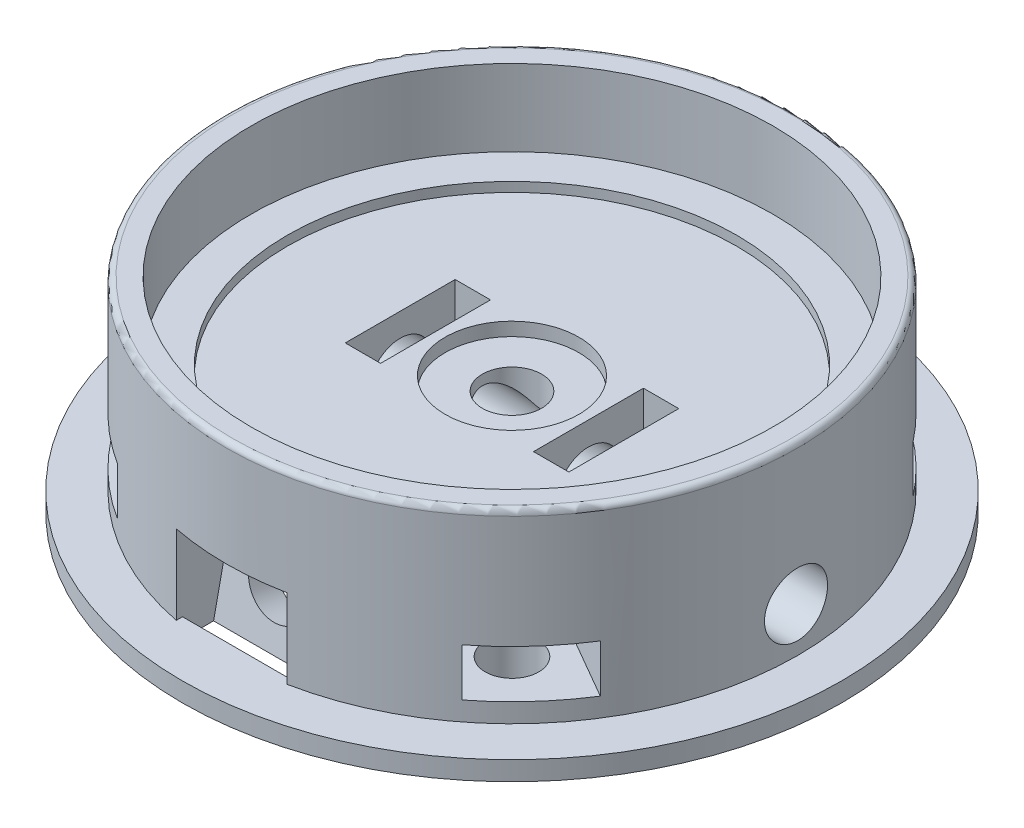
SolidWorks part; units mm, degrees
ref_plane "Front Plane" through (0, 0, 0) normal (0, 0, 1) x (1, 0, 0)
ref_plane "Top Plane" through (0, 0, 0) normal (0, 1, 0) x (1, 0, 0)
ref_plane "Right Plane" through (0, 0, 0) normal (1, 0, 0) x (0, 0, -1)
sketch "Sketch1" plane through (0, 0, 0) normal (0, 1, 0) x (1, 0, 0)
  circle A0 centre (0, 0) radius 14.95
  dimension "D1" = 29.9
extrude "Boss-Extrude1" add sketch "Sketch1" along normal blind 5.7
sketch "Sketch2" plane through (0, 5.7, 0) normal (0, 1, 0) x (1, 0, 0)
  circle A0 centre (0, 0) radius 11.75
  dimension "D1" = 23.5
extrude "Cut-Extrude1" cut sketch "Sketch2" against normal blind 0.5
sketch "Sketch3" plane through (0, 5.7, 0) normal (0, 1, 0) x (1, 0, 0)
  circle A0 centre (0, 0) radius 13.65
  circle A1 centre (0, 0) radius 14.95
  circle A2 centre (0, 0) radius 14.95 construction
  dimension "D1" = 27.3
extrude "Boss-Extrude2" add sketch "Sketch3" along normal blind 4
fillet "Fillet1" radius 0.3 1 edges at (0, 9.7, 14.95)
sketch "Sketch4" plane through (0, 5.2, 0) normal (0, 1, 0) x (1, 0, 0)
  circle A0 centre (0, 0) radius 1.55
  dimension "D1" = 3.1
extrude "Cut-Extrude2" cut sketch "Sketch4" against normal through all
ref_plane "Plane1" through (4, 0, 0) normal (1, 0, 0) x (0, 0, -1)
sketch "Sketch5" plane through (0, 0, 0) normal (1, 0, 0) x (0, 0, -1)
  line L1 (1.55, 5.2) -> (-1.55, 5.2) construction
  line L2 (-2.875, -0.55) -> (2.875, -0.55) construction
  line L3 (-2.875, -0.55) -> (-2.875, 5.2) construction
  line L4 (-2.875, 5.2) -> (2.875, 5.2) construction
  line L5 (2.875, -0.55) -> (2.875, 5.2) construction
  line L6 (-2.875, -0.55) -> (2.875, 5.2) construction
  line L7 (-2.875, 5.2) -> (2.875, -0.55) construction
  circle A0 centre (0, 2.325) radius 1.65
  dimension "D1" = 3.3
  dimension "D2" = 5.75
extrude "Cut-Extrude3" cut sketch "Sketch5" along normal through all
sketch "Sketch6" plane through (0, 0, 0) normal (0, -1, 0) x (1, 0, 0)
  circle A0 centre (0, 0) radius 1.55 construction
  circle A1 centre (0, 0) radius 1.55
  circle A2 centre (0, 0) radius 17.25
  dimension "D1" = 34.5
extrude "Boss-Extrude3" add sketch "Sketch6" along normal blind 1
sketch "Sketch7" plane through (4, 0, 0) normal (1, 0, 0) x (0, 0, -1)
  line L7 (-2.875, 5.2) -> (2.875, 5.2)
  line L8 (-2.875, 5.2) -> (-2.875, -0.55)
  line L9 (-2.875, -0.55) -> (2.875, -0.55)
  line L10 (2.875, 5.2) -> (2.875, -0.55)
  line L11 (-2.875, 5.2) -> (2.875, -0.55) construction
  line L12 (-2.875, -0.55) -> (2.875, 5.2) construction
  point P1 (0, 2.325)
  dimension "D2" = 5.75
extrude "Cut-Extrude4" cut sketch "Sketch7" along normal blind 1.85
ref_axis "Axis1" through (0, 9.4, 0) along (0, -1, 0)
pattern_circular "CirPattern1" count 2 over 360 about axis through (0, 9.4, 0) along (0, -1, 0) of "Cut-Extrude4", "Cut-Extrude3"
ref_plane "Plane2" through (0, 0, 0) normal (0, 0, 1) x (0, -1, 0)
ref_plane "Plane3" through (0, 0, 12.5) normal (0, 0, 1) x (0, -1, 0)
sketch "Sketch11" plane through (0, 0, 12.5) normal (0, 0, 1) x (0, -1, 0)
  line L0 (0, 23.2225) -> (0, -23.2225) construction
  point P4 (0, 0)
ref_plane "Plane4" through (0, 2.5421, 11.9597) normal (0, 0.2079, 0.9781) x (-1, 0, 0)
sketch "Sketch9" plane through (0, 0.4189, 12.411) normal (0, 0.2079, 0.9781) x (0, -0.9781, 0.2079)
  line L0 (-11.3652, 0) -> (-2.1706, 0) construction
  line L2 (1.4283, 2.9) -> (-4.3717, 2.9) construction
  line L3 (1.4283, 2.9) -> (1.4283, -2.9) construction
  line L4 (1.4283, -2.9) -> (-4.3717, -2.9) construction
  line L5 (-4.3717, 2.9) -> (-4.3717, -2.9) construction
  line L6 (1.4283, 2.9) -> (-4.3717, -2.9) construction
  line L7 (1.4283, -2.9) -> (-4.3717, 2.9) construction
  line L8 (0.4283, 23.2225) -> (0.4283, -23.2225) construction
  circle A0 centre (-1.4717, 0) radius 1.65
  dimension "D2" = 3.3
  dimension "D1" = 5.8
  dimension "D3" = 1
extrude "Cut-Extrude5" cut sketch "Sketch9" along normal through all and the other way blind 2
sketch "Sketch10" plane through (0, 0, 12.5) normal (0, 0.2079, 0.9781) x (0, -0.9781, 0.2079)
  line L1 (1, 2.9) -> (-4.8, 2.9) construction
  line L2 (-4.8, 2.9) -> (-4.8, -2.9) construction
  line L3 (1, -2.9) -> (-4.8, -2.9) construction
  line L5 (1, 2.9) -> (-4.8, 2.9)
  line L6 (-4.8, 2.9) -> (-4.8, -2.9)
  line L7 (1, -2.9) -> (-4.8, -2.9)
  line L8 (1, 2.9) -> (3, 2.9)
  line L9 (3, 2.9) -> (3, -2.9)
  line L10 (3, -2.9) -> (1, -2.9)
  dimension "D1" = 2
extrude "Cut-Extrude6" cut sketch "Sketch10" along normal blind 1.8
ref_plane "Plane5" through (0, 2.2302, 10.4924) normal (0, 0.2079, 0.9781) x (-1, 0, 0)
sketch "Sketch13" plane through (0, 2.2302, 10.4924) normal (0, 0.2079, 0.9781) x (-1, 0, 0)
  line L0 (-2.4902, -0.2075) -> (-3.8756, 3.5989)
  line L1 (-3.8756, 3.5989) -> (3.8756, 3.5989)
  line L2 (3.8756, 3.5989) -> (2.4902, -0.2075)
  line L3 (0, 0.6989) -> (0, 3.5989) construction
  line L4 (-2.9, 3.5989) -> (2.9, 3.5989) construction
  circle A0 centre (0, 0.6989) radius 1.65 construction
  circle A1 centre (0, 0.6989) radius 1.65 construction
  circle A2 centre (0, 0.6989) radius 2.65 construction
  arc A3 (2.4902, -0.2075) -> (-2.4902, -0.2075) centre (0, 0.6989) cw
  dimension "D1" = 20
  dimension "D2" = 1
ref_plane "Plane6" through (0, 0, 0) normal (-1, 0, 0) x (0, -1, 0)
ref_plane "Plane7" through (0, 0, 14.95) normal (0, 0, 1) x (1, 0, 0)
sketch "Sketch14" plane through (0, 0, 0) normal (-1, 0, 0) x (0, -1, 0)
  line L0 (-3.1606, 10.2947) -> (3.2723, 0) construction
  line L3 (0.0673, 10.9808) -> (-3.1606, 10.2947) construction
  line L5 (-3.1606, 10.2947) -> (-0.9985, 0.1229) construction
  arc A0 (-3.1606, 10.2947) -> (3.2723, 0) centre (14.1981, 13.9844) ccw
  dimension "D1" = 70
sweep "Cut-Sweep1" cut profiles "Sketch13" path "Sketch14"
sketch "Sketch19" plane through (0, 0, 14.95) normal (0, 0, 1) x (1, 0, 0)
  line L0 (2.9, 5.0693) -> (-2.9, 5.0693) construction
  line L1 (2.9, 5.0693) -> (-2.9, 5.0693) construction
  line L2 (14.95, 0) -> (-14.95, 0) construction
  line L3 (2.9, 0) -> (-2.9, 0) construction
  line L4 (-2.9, 5.0693) -> (-2.9, 0) construction
  line L5 (2.9, 5.0693) -> (2.9, 0) construction
  line L6 (-2.9, 4.1501) -> (2.9, 4.1501)
  line L7 (2.9, 4.1501) -> (2.9, 0)
  line L8 (2.9, 0) -> (-2.9, 0)
  line L9 (-2.9, 0) -> (-2.9, 4.1501)
  spline S0 degree 3 poles (-0.1103, 0.7763) (0.2206, 0.7763) (0.4399, 0.8212) (0.8405, 0.99) (1.0254, 1.1159) (1.2535, 1.3495) (1.3227, 1.4364) (1.4409, 1.6192) (1.4907, 1.7158) (1.5713, 1.9192) (1.6018, 2.0256) (1.6413, 2.2393) (1.6508, 2.3478) (1.6481, 2.6782) (1.6047, 2.8939) (1.4812, 3.1989) (1.431, 3.2954) (1.313, 3.4783) (1.2443, 3.5654) (1.0179, 3.8015) (0.8351, 3.9301) (0.4362, 4.1039) (0.2169, 4.1502) (-0.1103, 4.15) (-0.221, 4.1383) (-0.434, 4.0932) (-0.5375, 4.06) (-0.8386, 3.9282) (-1.0184, 3.8015) (-1.2465, 3.5629) (-1.3137, 3.4773) (-1.4313, 3.2948) (-1.4822, 3.1968) (-1.5641, 2.9938) (-1.5952, 2.8896) (-1.6378, 2.6758) (-1.6492, 2.5653) (-1.6515, 2.2381) (-1.6108, 2.0182) (-1.4501, 1.6141) (-1.3285, 1.4262) (-1.1006, 1.193) (-1.0155, 1.1217) (-0.835, 0.9992) (-0.7396, 0.9473) (-0.5381, 0.8627) (-0.4321, 0.8302) (-0.2188, 0.7873) (-0.1103, 0.7763) (0.2206, 0.7763) (0.4399, 0.8212) knots -0.03125 -0.03125 0 0 0.0625 0.0625 0.125 0.125 0.15625 0.15625 0.1875 0.1875 0.21875 0.21875 0.25 0.25 0.3125 0.3125 0.34375 0.34375 0.375 0.375 0.4375 0.4375 0.5 0.5 0.53125 0.53125 0.5625 0.5625 0.625 0.625 0.65625 0.65625 0.6875 0.6875 0.71875 0.71875 0.75 0.75 0.8125 0.8125 0.875 0.875 0.90625 0.90625 0.9375 0.9375 0.96875 0.96875 1 1 1.0625 1.0625 1.125 only from (0, 0.7763) to (0, 0.7763) construction
  spline S1 degree 3 poles (-0.1103, 0.7763) (0.2206, 0.7763) (0.4399, 0.8212) (0.8405, 0.99) (1.0254, 1.1159) (1.2535, 1.3495) (1.3227, 1.4364) (1.4409, 1.6192) (1.4907, 1.7158) (1.5713, 1.9192) (1.6018, 2.0256) (1.6413, 2.2393) (1.6508, 2.3478) (1.6481, 2.6782) (1.6047, 2.8939) (1.4812, 3.1989) (1.431, 3.2954) (1.313, 3.4783) (1.2443, 3.5654) (1.0179, 3.8015) (0.8351, 3.9301) (0.4362, 4.1039) (0.2169, 4.1502) (-0.1103, 4.15) (-0.221, 4.1383) (-0.434, 4.0932) (-0.5375, 4.06) (-0.8386, 3.9282) (-1.0184, 3.8015) (-1.2465, 3.5629) (-1.3137, 3.4773) (-1.4313, 3.2948) (-1.4822, 3.1968) (-1.5641, 2.9938) (-1.5952, 2.8896) (-1.6378, 2.6758) (-1.6492, 2.5653) (-1.6515, 2.2381) (-1.6108, 2.0182) (-1.4501, 1.6141) (-1.3285, 1.4262) (-1.1006, 1.193) (-1.0155, 1.1217) (-0.835, 0.9992) (-0.7396, 0.9473) (-0.5381, 0.8627) (-0.4321, 0.8302) (-0.2188, 0.7873) (-0.1103, 0.7763) (0.2206, 0.7763) (0.4399, 0.8212) knots -0.03125 -0.03125 0 0 0.0625 0.0625 0.125 0.125 0.15625 0.15625 0.1875 0.1875 0.21875 0.21875 0.25 0.25 0.3125 0.3125 0.34375 0.34375 0.375 0.375 0.4375 0.4375 0.5 0.5 0.53125 0.53125 0.5625 0.5625 0.625 0.625 0.65625 0.65625 0.6875 0.6875 0.71875 0.71875 0.75 0.75 0.8125 0.8125 0.875 0.875 0.90625 0.90625 0.9375 0.9375 0.96875 0.96875 1 1 1.0625 1.0625 1.125 only from (0, 0.7763) to (0, 0.7763) construction
extrude "Cut-Extrude11" cut sketch "Sketch19" against normal up to surface (0.6098 mm away) up to face at (0, 2.0347, 13.9077)
pattern_circular "CirPattern2" count 2 over 360 about axis through (0, 9.4, 0) along (0, -1, 0) of "Cut-Extrude5", "Cut-Sweep1", "Cut-Extrude6", "Cut-Extrude11"
sketch "Sketch16" plane through (0, -1, 0) normal (0, -1, 0) x (1, 0, 0)
  line L0 (0, 0) -> (-12.1976, 12.1976) construction
  line L1 (0, 11.1539) -> (0, -11.1539) construction
  circle A0 centre (0, 0) radius 17.25 construction
  circle A1 centre (-8.5206, 8.5206) radius 1.4
  circle A2 centre (-8.5206, 8.5206) radius 2.9 construction
  circle A3 centre (0, 0) radius 14.95 construction
  dimension "D2" = 2.8
  dimension "D3" = 5.8
  dimension "D1" = 45
extrude "Cut-Extrude8" cut sketch "Sketch16" against normal blind 4.5
sketch "Sketch17" plane through (0, 3.5, 0) normal (0, -1, 0) x (1, 0, 0)
  line L0 (0, 11.1539) -> (0, -11.1539) construction
  line L1 (-9.964, 11.0206) -> (-11.4074, 8.5206) construction
  line L2 (-11.4074, 8.5206) -> (-9.964, 6.0206)
  line L3 (-9.964, 6.0206) -> (-7.0773, 6.0206)
  line L4 (-7.0773, 6.0206) -> (-5.6339, 8.5206)
  line L5 (-5.6339, 8.5206) -> (-7.0773, 11.0206)
  line L6 (-7.0773, 11.0206) -> (-9.964, 11.0206) construction
  line L7 (-7.0773, 11.0206) -> (-8.0109, 12.6377)
  line L8 (-8.0109, 12.6377) -> (-12.341, 10.1377)
  line L9 (-12.341, 10.1377) -> (-11.4074, 8.5206)
  circle A0 centre (-8.5206, 8.5206) radius 2.5 construction
  circle A1 centre (0, 0) radius 14.95 construction
  dimension "D1" = 5
  dimension "D2" = 30
extrude "Cut-Extrude9" cut sketch "Sketch17" along normal blind 2.5
pattern_circular "CirPattern3" count 4 over 360 about axis through (0, 9.4, 0) along (0, -1, 0) of "Cut-Extrude8", "Cut-Extrude9"
sketch "Sketch18" plane through (0, 5.2, 0) normal (0, 1, 0) x (1, 0, 0)
  circle A2 centre (0, 0) radius 3.5
  dimension "D1" = 7
extrude "Cut-Extrude10" cut sketch "Sketch18" against normal blind 0.7
